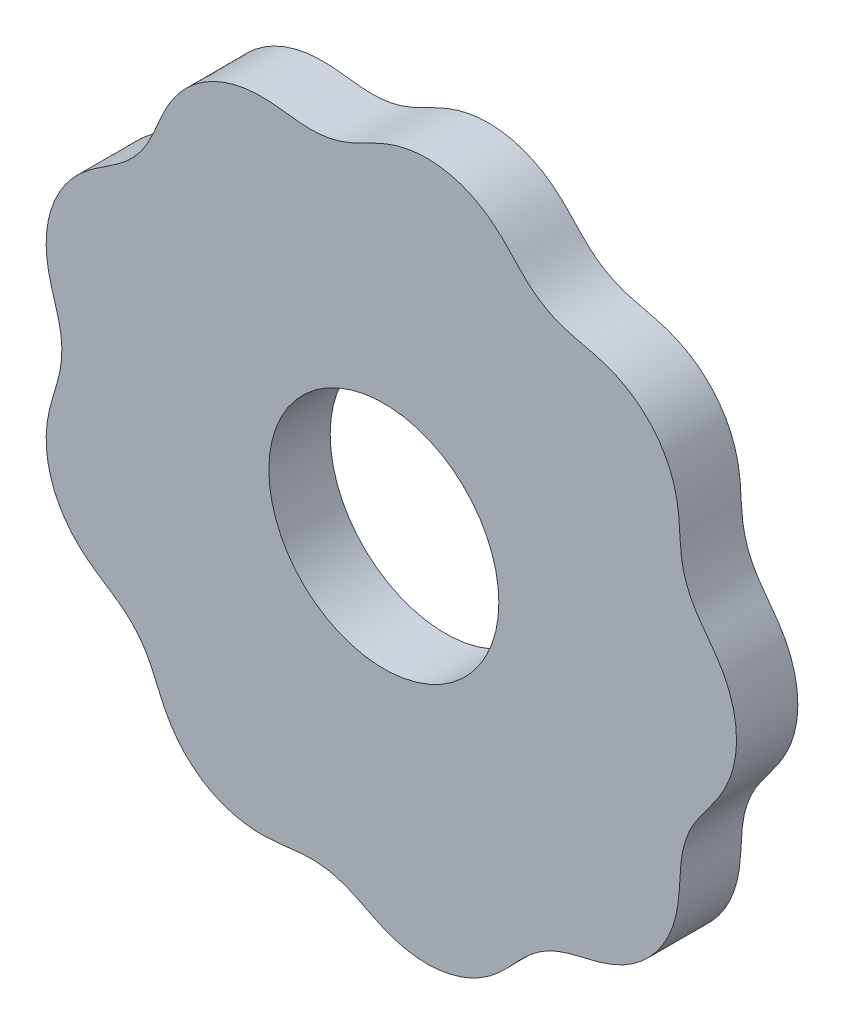
SolidWorks part; units mm, degrees
ref_plane "前视基准面" through (0, 0, 0) normal (0, 0, 1) x (1, 0, 0)
ref_plane "上视基准面" through (0, 0, 0) normal (0, 1, 0) x (1, 0, 0)
ref_plane "右视基准面" through (0, 0, 0) normal (1, 0, 0) x (0, 0, -1)
other "Configuration Table"
ref_axis "基准轴1" through (0, 0, 55) along (0, 0, -1)
sketch "LobeBaseSketch" plane through (0, 0, 0) normal (0, 0, 1) x (1, 0, 0)
  circle A0 centre (0, 0) radius 7.5
  spline S0 degree 3 poles (22.9912, -0.4231) (23.0044, 0) (22.9912, 0.4231) (22.952, 0.8425) (22.8876, 1.2549) (22.7995, 1.6568) (22.6896, 2.0458) (22.5603, 2.4195) (22.4141, 2.7767) (22.2534, 3.1166) (22.0808, 3.4397) (21.8982, 3.7475) (21.7071, 4.0424) (21.5082, 4.3286) (21.3014, 4.6114) (21.086, 4.898) (20.8609, 5.1973) (20.6265, 5.5195) (20.3856, 5.8749) (20.1462, 6.271) (19.9214, 6.7089) (19.7266, 7.1799) (19.5731, 7.6659) (19.4638, 8.1459) (19.3925, 8.6032) (19.3487, 9.0302) (19.3212, 9.4278) (19.3012, 9.8017) (19.282, 10.1597) (19.2586, 10.5093) (19.227, 10.8564) (19.1838, 11.2051) (19.1259, 11.5582) (19.0504, 11.9167) (18.955, 12.2804) (18.8375, 12.648) (18.6963, 13.0174) (18.5304, 13.386) (18.3395, 13.7506) (18.1238, 14.1078) (17.8843, 14.4544) (17.6224, 14.7869) (17.3403, 15.1026) (17.0406, 15.3987) (16.7263, 15.6731) (16.4004, 15.9244) (16.0662, 16.1518) (15.7269, 16.355) (15.3853, 16.5345) (15.0438, 16.6917) (14.7038, 16.8282) (14.3661, 16.9466) (14.0301, 17.0497) (13.6939, 17.1411) (13.3537, 17.2248) (13.0044, 17.3059) (12.6396, 17.3905) (12.2529, 17.4866) (11.84, 17.604) (11.402, 17.7536) (10.9483, 17.9446) (10.4963, 18.1801) (10.0663, 18.4538) (9.6741, 18.7512) (9.3255, 19.0557) (9.0174, 19.3546) (8.7409, 19.6415) (8.4852, 19.9151) (8.2403, 20.177) (7.9977, 20.4298) (7.7504, 20.6753) (7.4931, 20.9147) (7.2218, 21.148) (6.9335, 21.3741) (6.6267, 21.5914) (6.3003, 21.7974) (5.9547, 21.9897) (5.5908, 22.1654) (5.2102, 22.3219) (4.8153, 22.457) (4.409, 22.5685) (3.9947, 22.6549) (3.5757, 22.7154) (3.1558, 22.7496) (2.7386, 22.7577) (2.3274, 22.7408) (1.9253, 22.7002) (1.5348, 22.6377) (1.1577, 22.5557) (0.795, 22.4565) (0.4468, 22.3426) (0.112, 22.2162) (-0.2116, 22.0792) (-0.528, 21.9331) (-0.8424, 21.7785) (-1.1621, 21.6161) (-1.4959, 21.4465) (-1.8539, 21.2716) (-2.2457, 21.096) (-2.6774, 20.9291) (-3.1477, 20.7838) (-3.6453, 20.6736) (-4.1506, 20.6069) (-4.6423, 20.5826) (-5.105, 20.5919) (-5.5332, 20.6228) (-5.9294, 20.6648) (-6.3012, 20.71) (-6.6571, 20.7532) (-7.0054, 20.7909) (-7.3527, 20.8201) (-7.7037, 20.8381) (-8.0615, 20.8424) (-8.4276, 20.8303) (-8.8024, 20.7995) (-9.1848, 20.7476) (-9.5731, 20.6727) (-9.9649, 20.5733) (-10.357, 20.4486) (-10.7463, 20.2983) (-11.1292, 20.1225) (-11.5022, 19.9224) (-11.862, 19.6994) (-12.2056, 19.4557) (-12.5305, 19.1938) (-12.8346, 18.9165) (-13.1165, 18.6269) (-13.3755, 18.328) (-13.6117, 18.0228) (-13.8258, 17.7137) (-14.0193, 17.4026) (-14.1945, 17.0906) (-14.3544, 16.7776) (-14.5027, 16.4623) (-14.6443, 16.1418) (-14.7848, 15.812) (-14.9315, 15.4674) (-15.0933, 15.1033) (-15.2806, 14.717) (-15.5039, 14.3116) (-15.7708, 13.898) (-16.0812, 13.4938) (-16.4254, 13.1179) (-16.7864, 12.7832) (-17.1469, 12.4928) (-17.4947, 12.2413) (-17.8253, 12.0188) (-18.1391, 11.8145) (-18.4396, 11.6188) (-18.7306, 11.4237) (-19.0154, 11.2229) (-19.2958, 11.0111) (-19.5727, 10.7844) (-19.8454, 10.5398) (-20.1126, 10.2753) (-20.3722, 9.9897) (-20.6216, 9.6827) (-20.8578, 9.3548) (-21.0781, 9.0072) (-21.2796, 8.6418) (-21.46, 8.261) (-21.6171, 7.868) (-21.7494, 7.4659) (-21.856, 7.0583) (-21.9364, 6.6488) (-21.9912, 6.2409) (-22.021, 5.8379) (-22.0273, 5.4425) (-22.012, 5.0568) (-21.9773, 4.6824) (-21.9256, 4.3198) (-21.8592, 3.9681) (-21.7805, 3.6256) (-21.6915, 3.2887) (-21.5939, 2.9522) (-21.4895, 2.6092) (-21.3805, 2.251) (-21.2703, 1.868) (-21.1655, 1.4517) (-21.076, 0.9976) (-21.0146, 0.5092) (-20.9926, 0) (-21.0146, -0.5092) (-21.076, -0.9976) (-21.1655, -1.4517) (-21.2703, -1.868) (-21.3805, -2.251) (-21.4895, -2.6092) (-21.5939, -2.9522) (-21.6915, -3.2887) (-21.7805, -3.6256) (-21.8592, -3.9681) (-21.9256, -4.3198) (-21.9773, -4.6824) (-22.012, -5.0568) (-22.0273, -5.4425) (-22.021, -5.8379) (-21.9912, -6.2409) (-21.9364, -6.6488) (-21.856, -7.0583) (-21.7494, -7.4659) (-21.6171, -7.868) (-21.46, -8.261) (-21.2796, -8.6418) (-21.0781, -9.0072) (-20.8578, -9.3548) (-20.6216, -9.6827) (-20.3722, -9.9897) (-20.1126, -10.2753) (-19.8454, -10.5398) (-19.5727, -10.7844) (-19.2958, -11.0111) (-19.0154, -11.2229) (-18.7306, -11.4237) (-18.4396, -11.6188) (-18.1391, -11.8145) (-17.8253, -12.0188) (-17.4947, -12.2413) (-17.1469, -12.4928) (-16.7864, -12.7832) (-16.4254, -13.1179) (-16.0812, -13.4938) (-15.7708, -13.898) (-15.5039, -14.3116) (-15.2806, -14.717) (-15.0933, -15.1033) (-14.9315, -15.4674) (-14.7848, -15.812) (-14.6443, -16.1418) (-14.5027, -16.4623) (-14.3544, -16.7776) (-14.1945, -17.0906) (-14.0193, -17.4026) (-13.8258, -17.7137) (-13.6117, -18.0228) (-13.3755, -18.328) (-13.1165, -18.6269) (-12.8346, -18.9165) (-12.5305, -19.1938) (-12.2056, -19.4557) (-11.862, -19.6994) (-11.5022, -19.9224) (-11.1292, -20.1225) (-10.7463, -20.2983) (-10.357, -20.4486) (-9.9649, -20.5733) (-9.5731, -20.6727) (-9.1848, -20.7476) (-8.8024, -20.7995) (-8.4276, -20.8303) (-8.0615, -20.8424) (-7.7037, -20.8381) (-7.3527, -20.8201) (-7.0054, -20.7909) (-6.6571, -20.7532) (-6.3012, -20.71) (-5.9294, -20.6648) (-5.5332, -20.6228) (-5.105, -20.5919) (-4.6423, -20.5826) (-4.1506, -20.6069) (-3.6453, -20.6736) (-3.1477, -20.7838) (-2.6774, -20.9291) (-2.2457, -21.096) (-1.8539, -21.2716) (-1.4959, -21.4465) (-1.1621, -21.6161) (-0.8424, -21.7785) (-0.528, -21.9331) (-0.2116, -22.0792) (0.112, -22.2162) (0.4468, -22.3426) (0.795, -22.4565) (1.1577, -22.5557) (1.5348, -22.6377) (1.9253, -22.7002) (2.3274, -22.7408) (2.7386, -22.7577) (3.1558, -22.7496) (3.5757, -22.7154) (3.9947, -22.6549) (4.409, -22.5685) (4.8153, -22.457) (5.2102, -22.3219) (5.5908, -22.1654) (5.9547, -21.9897) (6.3003, -21.7974) (6.6267, -21.5914) (6.9335, -21.3741) (7.2218, -21.148) (7.4931, -20.9147) (7.7504, -20.6753) (7.9977, -20.4298) (8.2403, -20.177) (8.4852, -19.9151) (8.7409, -19.6415) (9.0174, -19.3546) (9.3255, -19.0557) (9.6741, -18.7512) (10.0663, -18.4538) (10.4963, -18.1801) (10.9483, -17.9446) (11.402, -17.7536) (11.84, -17.604) (12.2529, -17.4866) (12.6396, -17.3905) (13.0044, -17.3059) (13.3537, -17.2248) (13.6939, -17.1411) (14.0301, -17.0497) (14.3661, -16.9466) (14.7038, -16.8282) (15.0438, -16.6917) (15.3853, -16.5345) (15.7269, -16.355) (16.0662, -16.1518) (16.4004, -15.9244) (16.7263, -15.6731) (17.0406, -15.3987) (17.3403, -15.1026) (17.6224, -14.7869) (17.8843, -14.4544) (18.1238, -14.1078) (18.3395, -13.7506) (18.5304, -13.386) (18.6963, -13.0174) (18.8375, -12.648) (18.955, -12.2804) (19.0504, -11.9167) (19.1259, -11.5582) (19.1838, -11.2051) (19.227, -10.8564) (19.2586, -10.5093) (19.282, -10.1597) (19.3012, -9.8017) (19.3212, -9.4278) (19.3487, -9.0302) (19.3925, -8.6032) (19.4638, -8.1459) (19.5731, -7.6659) (19.7266, -7.1799) (19.9214, -6.7089) (20.1462, -6.271) (20.3856, -5.8749) (20.6265, -5.5195) (20.8609, -5.1973) (21.086, -4.898) (21.3014, -4.6114) (21.5082, -4.3286) (21.7071, -4.0424) (21.8982, -3.7475) (22.0808, -3.4397) (22.2534, -3.1166) (22.4141, -2.7767) (22.5603, -2.4195) (22.6896, -2.0458) (22.7995, -1.6568) (22.8876, -1.2549) (22.952, -0.8425) (22.9912, -0.4231) (23.0044, 0) (22.9912, 0.4231) knots -0.008737 -0.005848 -0.002931 0 0.002931 0.005848 0.008737 0.011586 0.014383 0.017119 0.019789 0.022388 0.024919 0.027388 0.029811 0.032211 0.034619 0.037082 0.039652 0.04239 0.04535 0.048558 0.051989 0.055556 0.059122 0.062553 0.065761 0.068721 0.071459 0.07403 0.076492 0.0789 0.0813 0.083723 0.086192 0.088723 0.091322 0.093992 0.096728 0.099525 0.102374 0.105263 0.10818 0.111111 0.114042 0.116959 0.119848 0.122697 0.125494 0.12823 0.1309 0.133499 0.13603 0.1385 0.140923 0.143322 0.14573 0.148193 0.150763 0.153501 0.156461 0.159669 0.1631 0.166667 0.170233 0.173664 0.176872 0.179832 0.18257 0.185141 0.187603 0.190012 0.192411 0.194834 0.197304 0.199834 0.202434 0.205103 0.207839 0.210636 0.213485 0.216374 0.219291 0.222222 0.225153 0.22807 0.230959 0.233808 0.236605 0.239342 0.242011 0.24461 0.247141 0.249611 0.252034 0.254433 0.256841 0.259304 0.261874 0.264612 0.267572 0.27078 0.274212 0.277778 0.281344 0.284775 0.287983 0.290943 0.293681 0.296252 0.298714 0.301123 0.303522 0.305945 0.308415 0.310945 0.313545 0.316214 0.31895 0.321748 0.324596 0.327486 0.330402 0.333333 0.336264 0.339181 0.34207 0.344919 0.347716 0.350453 0.353122 0.355721 0.358252 0.360722 0.363145 0.365544 0.367953 0.370415 0.372985 0.375724 0.378683 0.381891 0.385323 0.388889 0.392455 0.395886 0.399094 0.402054 0.404793 0.407363 0.409825 0.412234 0.414633 0.417056 0.419526 0.422057 0.424656 0.427325 0.430062 0.432859 0.435707 0.438597 0.441513 0.444444 0.447375 0.450292 0.453181 0.45603 0.458827 0.461564 0.464233 0.466832 0.469363 0.471833 0.474256 0.476655 0.479064 0.481526 0.484096 0.486835 0.489795 0.493002 0.496434 0.5 0.503566 0.506998 0.510205 0.513165 0.515904 0.518474 0.520936 0.523345 0.525744 0.528167 0.530637 0.533168 0.535767 0.538436 0.541173 0.54397 0.546819 0.549708 0.552625 0.555556 0.558487 0.561403 0.564293 0.567141 0.569938 0.572675 0.575344 0.577943 0.580474 0.582944 0.585367 0.587766 0.590175 0.592637 0.595207 0.597946 0.600906 0.604114 0.607545 0.611111 0.614677 0.618109 0.621317 0.624276 0.627015 0.629585 0.632047 0.634456 0.636855 0.639278 0.641748 0.644279 0.646878 0.649547 0.652284 0.655081 0.65793 0.660819 0.663736 0.666667 0.669598 0.672514 0.675404 0.678252 0.68105 0.683786 0.686455 0.689055 0.691585 0.694055 0.696478 0.698877 0.701286 0.703748 0.706319 0.709057 0.712017 0.715225 0.718656 0.722222 0.725788 0.72922 0.732428 0.735388 0.738126 0.740696 0.743159 0.745567 0.747966 0.750389 0.752859 0.75539 0.757989 0.760658 0.763395 0.766192 0.769041 0.77193 0.774847 0.777778 0.780709 0.783626 0.786515 0.789364 0.792161 0.794897 0.797566 0.800166 0.802696 0.805166 0.807589 0.809988 0.812397 0.814859 0.81743 0.820168 0.823128 0.826336 0.829767 0.833333 0.8369 0.840331 0.843539 0.846499 0.849237 0.851807 0.85427 0.856678 0.859077 0.8615 0.86397 0.866501 0.8691 0.87177 0.874506 0.877303 0.880152 0.883041 0.885958 0.888889 0.89182 0.894737 0.897626 0.900475 0.903272 0.906008 0.908678 0.911277 0.913808 0.916277 0.9187 0.9211 0.923508 0.92597 0.928541 0.931279 0.934239 0.937447 0.940878 0.944444 0.948011 0.951442 0.95465 0.95761 0.960348 0.962918 0.965381 0.967789 0.970189 0.972612 0.975081 0.977612 0.980211 0.982881 0.985617 0.988414 0.991263 0.994152 0.997069 1 1.002931 1.005848 1.008737 only from (23, 0) to (23, 0)
extrude "LobeBase" add sketch "LobeBaseSketch" along normal blind 2 and the other way blind 2
sketch "BoreRevolveSketch" plane through (0, 0, 0) normal (1, 0, 0) x (0, 0, -1)
  line L0 (0, 0) -> (1, 0) construction
  line L1 (-2, 0) -> (2, 0)
  line L2 (2, 0) -> (2, 7.5)
  line L3 (2, 7.5) -> (-2, 7.5)
  line L4 (-2, 7.5) -> (-2, 0)
  dimension "TaperSide1" = 7.5
  dimension "TaperSide2" = 7.5
sketch "AuxiliarySketchCycloidal01" plane through (0, 0, 0) normal (0, 0, 1) x (1, 0, 0)
  circle A0 centre (0, 0) radius 22.5 construction
  circle A1 centre (25, 0) radius 2.5 construction
  circle A2 centre (0, 0) radius 25 construction
  circle A3 centre (25, 0) radius 3 construction
  circle A4 centre (26, 0) radius 0.3 construction
  spline S0 degree 3 poles (26, 0) (26, 0.4059) (25.9623, 1.0121) (25.8383, 1.8065) (25.7118, 2.3842) (25.5544, 2.9419) (25.3699, 3.4756) (25.1627, 3.9823) (24.9374, 4.4595) (24.6993, 4.9057) (24.4536, 5.3204) (24.2056, 5.7039) (23.9603, 6.0574) (23.7226, 6.383) (23.4967, 6.6838) (23.2864, 6.9633) (23.0948, 7.2259) (22.9241, 7.4764) (22.7758, 7.72) (22.6508, 7.9619) (22.549, 8.2072) (22.4693, 8.4605) (22.4096, 8.7262) (22.3666, 9.0081) (22.3363, 9.3097) (22.3144, 9.6341) (22.2958, 9.9833) (22.2755, 10.3589) (22.2483, 10.7612) (22.2089, 11.1896) (22.1525, 11.6428) (22.0741, 12.1184) (21.9697, 12.6133) (21.8355, 13.1236) (21.6686, 13.645) (21.4668, 14.1724) (21.2289, 14.7008) (20.9545, 15.2246) (20.5388, 15.9129) (20.1781, 16.4016) (19.9172, 16.7125) knots 0 0 0 0 0.067052 0.100157 0.132762 0.164708 0.195842 0.226021 0.255111 0.282993 0.309561 0.33473 0.358435 0.380641 0.401343 0.420578 0.438433 0.455054 0.470654 0.48552 0.5 0.51448 0.529346 0.544946 0.561567 0.579422 0.598657 0.619359 0.641565 0.66527 0.690439 0.717007 0.744889 0.773979 0.804158 0.835292 0.867238 0.899843 0.932948 1 1 1 1 construction
